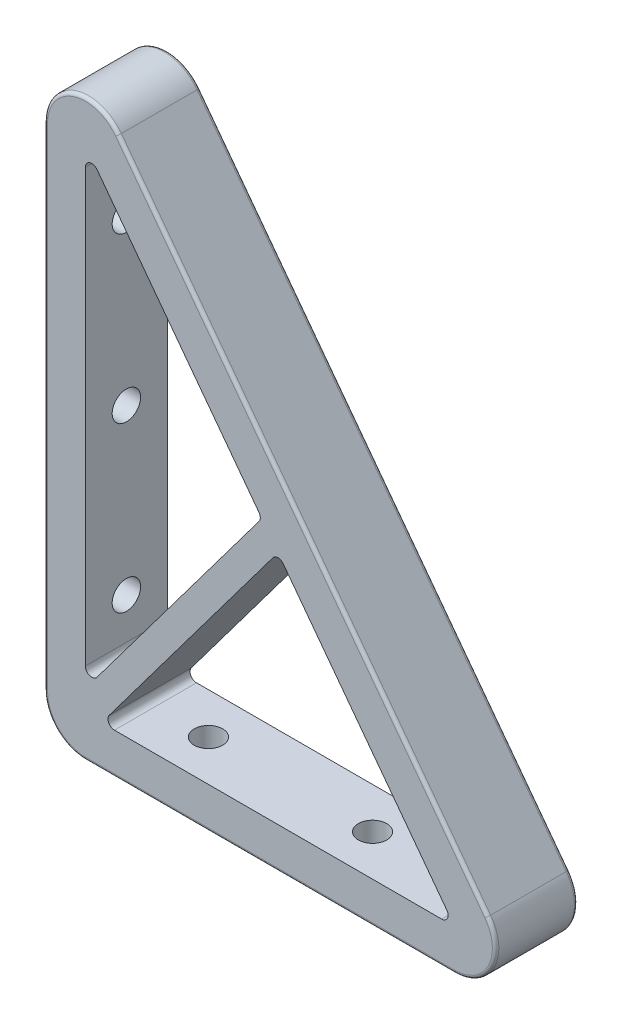
SolidWorks part; units mm, degrees
ref_plane "Front Plane" through (0, 0, 0) normal (0, 0, 1) x (1, 0, 0)
ref_plane "Top Plane" through (0, 0, 0) normal (0, 1, 0) x (1, 0, 0)
ref_plane "Right Plane" through (0, 0, 0) normal (1, 0, 0) x (0, 0, -1)
sketch "Sketch1" plane through (0, 0, 0) normal (0, 0, 1) x (1, 0, 0)
  line L0 (0, 0) -> (76.2, -101.6)
  line L1 (0, 0) -> (76.2, 0)
  line L2 (0, 0) -> (0, -101.6)
  line L3 (0, -101.6) -> (76.2, -101.6)
  line L4 (76.2, 0) -> (76.2, -101.6)
  line L5 (6.35, -19.05) -> (6.35, -95.25)
  line L6 (6.35, -95.25) -> (63.5, -95.25)
  line L7 (63.5, -95.25) -> (6.35, -19.05)
  line L8 (6.35, -95.25) -> (34.925, -57.15) construction
  line L9 (8.85, -95.25) -> (36.175, -58.8167)
  line L10 (6.35, -91.9167) -> (33.675, -55.4833)
  dimension "D1" = 101.6
  dimension "D2" = 76.2
  dimension "D3" = 6.35
  dimension "D4" = 6.35
  dimension "D5" = 6.35
  dimension "D6" = 4
  dimension "D7" = 2
extrude "Boss-Extrude1" add sketch "Sketch1" along normal blind 12.7 contours L2 L3 L0 L7 L6 L5 | L8 L6 L9 L7 | L5 L8 L7 L10 region at (37.084, -51.562, 0) region at (20.3273, -74.9593, 0) region at (21.568, -76.6136, 0)
fillet "Fillet1" radius 6.35 3 edges at (0, 0, 6.35) (76.2, -101.6, 6.35) (0, -101.6, 6.35)
fillet "Fillet2" radius 1 6 edges at (63.5, -95.25, 6.35) (6.35, -19.05, 6.35) (36.175, -58.8167, 6.35) (33.675, -55.4833, 6.35) (6.35, -91.9167, 6.35) (8.85, -95.25, 6.35)
sketch "Sketch2" plane through (0, -101.6, 0) normal (0, -1, 0) x (1, 0, 0)
  line L0 (0, 0) -> (0, 12.7) construction
  line L1 (6.35, 12.7) -> (63.5, 12.7) construction
  circle A0 centre (19.05, 6.35) radius 2.2
  circle A1 centre (44.45, 6.35) radius 2.2
  point P8 (0, 0)
  dimension "D4" = 4.4
  dimension "D1" = 19.05
  dimension "D2" = 25.4
  dimension "D3" = 6.35
extrude "Cut-Extrude1" cut sketch "Sketch2" against normal up to next
sketch "Sketch3" plane through (0, 0, 0) normal (-1, 0, 0) x (0, 0, 1)
  line L0 (12.7, -19.05) -> (12.7, -95.25) construction
  line L1 (12.7, -101.6) -> (0, -101.6) construction
  circle A0 centre (6.35, -82.55) radius 2.2
  circle A1 centre (6.35, -57.15) radius 2.2
  circle A2 centre (6.35, -31.75) radius 2.2
  dimension "D1" = 4.4
  dimension "D2" = 6.35
  dimension "D3" = 19.05
  dimension "D4" = 25.4
  dimension "D5" = 25.4
extrude "Cut-Extrude2" cut sketch "Sketch3" against normal up to next
fillet "Fillet3" radius 0.5 12 edges at (4.342, -13.0259, 0) (40.005, -53.34, 0) (69.1796, -98.0898, 0) (34.925, -101.6, 0) (1.8599, -99.7401, 0) (4.342, -13.0259, 12.7) (0, -57.15, 12.7) (1.8599, -99.7401, 12.7) (34.925, -101.6, 12.7) (69.1796, -98.0898, 12.7) (0, -57.15, 0) (40.005, -53.34, 12.7)
